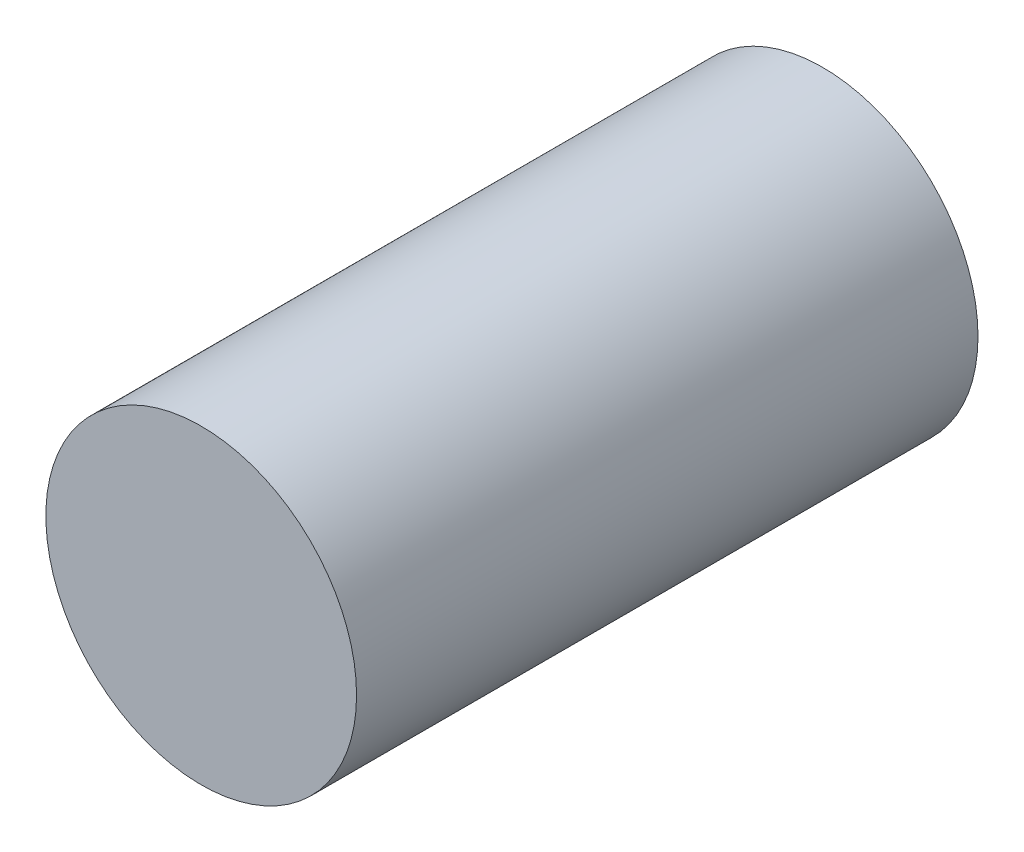
SolidWorks part; units mm, degrees
ref_plane "Front Plane" through (0, 0, 0) normal (0, 0, 1) x (1, 0, 0)
ref_plane "Top Plane" through (0, 0, 0) normal (0, 1, 0) x (1, 0, 0)
ref_plane "Right Plane" through (0, 0, 0) normal (1, 0, 0) x (0, 0, -1)
sketch "Sketch1" plane through (0, 0, 0) normal (0, 0, 1) x (1, 0, 0)
  circle A0 centre (0, 0) radius 2.5
  dimension "D1" = 5
extrude "Boss-Extrude1" add sketch "Sketch1" along normal blind 10
ref_axis "Axis1" through (0, 0, -0.5) along (0, 0, 1)
